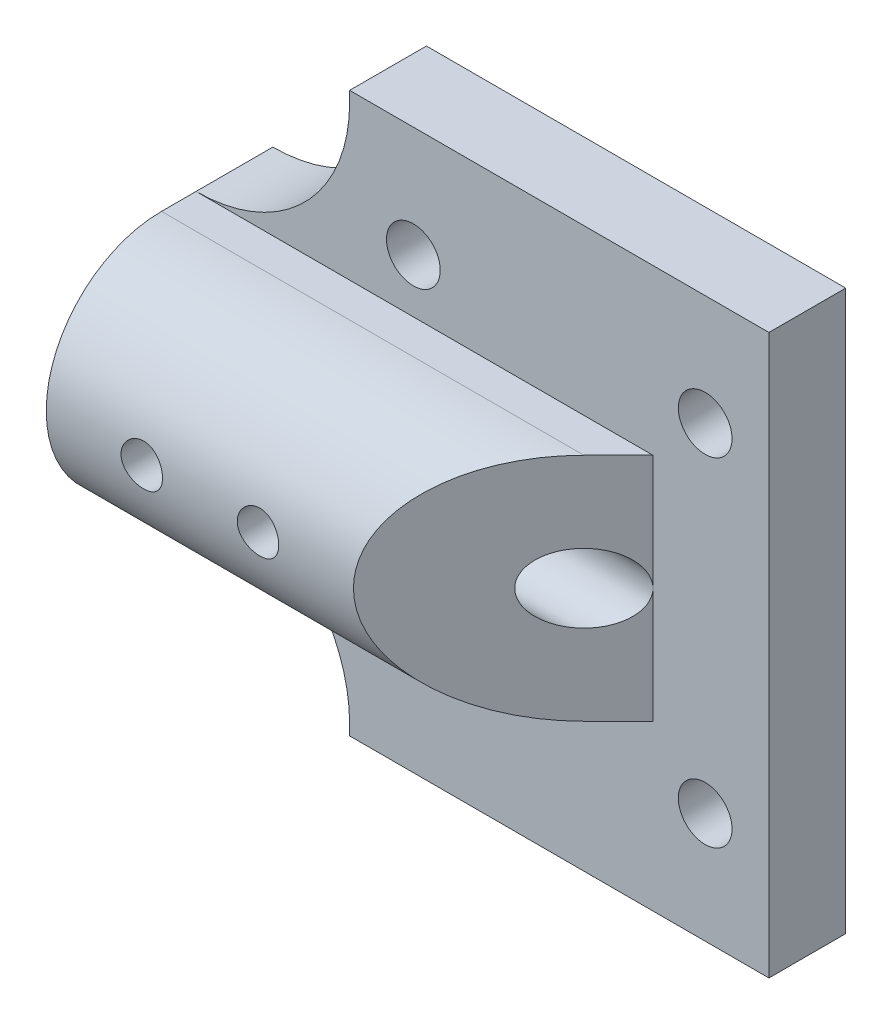
SolidWorks part; units mm, degrees
ref_plane "Front Plane" through (0, 0, 0) normal (0, 0, 1) x (1, 0, 0)
ref_plane "Top Plane" through (0, 0, 0) normal (0, 1, 0) x (1, 0, 0)
ref_plane "Right Plane" through (0, 0, 0) normal (1, 0, 0) x (0, 0, -1)
sketch "Sketch1" plane through (0, 0, 0) normal (0, 0, 1) x (1, 0, 0)
  line L0 (0, 18.2) -> (0, -18.2) construction
  line L1 (-13.65, -18.2) -> (13.65, -18.2)
  line L2 (-13.65, -18.2) -> (-13.65, 18.2) construction
  line L3 (-13.65, 18.2) -> (13.65, 18.2)
  line L4 (13.65, -18.2) -> (13.65, 18.2)
  line L5 (-13.65, -18.2) -> (13.65, 18.2) construction
  line L6 (-13.65, 18.2) -> (13.65, -18.2) construction
  line L7 (-13.65, 0) -> (13.65, 0) construction
  line L8 (-13.65, 0) -> (-23.65, 0) construction
  line L9 (-23.65, 2) -> (-23.65, -2) construction
  line L10 (-13.65, 2) -> (-23.65, 2) construction
  line L11 (-13.65, -2) -> (-23.65, -2) construction
  line L12 (-23.65, -7.5) -> (-23.65, 7.5)
  line L13 (-23.65, 7.5) -> (-13.65, 7.5)
  line L14 (-13.65, 7.5) -> (-13.65, 18.2)
  line L15 (-23.65, -7.5) -> (-13.65, -7.5)
  line L16 (-13.65, -7.5) -> (-13.65, -18.2)
  circle A0 centre (-9.5, 11) radius 1.75
  circle A1 centre (9.5, 11) radius 1.75
  circle A2 centre (-9.5, -11) radius 1.75
  circle A3 centre (9.5, -11) radius 1.75
  point P0 (0, 0)
  point P22 (-23.65, 0)
  point P27 (-23.65, 0)
  dimension "D3" = 3.5
  dimension "D4" = 11
  dimension "D5" = 9.5
  dimension "D1" = 36.4
  dimension "D2" = 27.3
  dimension "D6" = 4
  dimension "D7" = 10
  dimension "D8" = 15
extrude "Boss-Extrude1" add sketch "Sketch1" along normal blind 5
sketch "Sketch2" plane through (-23.65, 0, 0) normal (-1, 0, 0) x (0, 0, 1)
  line L0 (0, 0) -> (50000, 0) construction
  line L2 (5, 7.5) -> (5, -7.5) construction
  line L3 (5, 7.5) -> (5, -7.5)
  line L4 (5, 7.5) -> (7.25, 7.5)
  line L6 (7.25, -7.5) -> (5, -7.5)
  circle A0 centre (7.25, 0) radius 2.25 construction
  arc A1 (7.25, -7.5) -> (7.25, 7.5) centre (7.25, 0) ccw
  point P9 (9.5, 0)
  dimension "D1" = 4.5
  dimension "D3" = 15
extrude "Boss-Extrude4" add sketch "Sketch2" against normal blind 20
ref_plane "Plane1" through (0, 0, 14.75) normal (0, 0, 1) x (1, 0, 0)
sketch "Sketch7" plane through (0, 0, 14.75) normal (0, 0, 1) x (1, 0, 0)
  line L0 (-23.65, 0) -> (-18.7833, 0) construction
  line L1 (-23.65, 7.5) -> (-23.65, -7.5) construction
  line L2 (-16.0833, 0) -> (-11.2167, 0) construction
  line L3 (-8.5167, 0) -> (-3.65, 0) construction
  line L4 (-3.65, -7.5) -> (-3.65, 7.5) construction
  circle A0 centre (-17.4333, 0) radius 1.35
  circle A1 centre (-9.8667, 0) radius 1.35
  dimension "D1" = 2.7
extrude "Cut-Extrude3" cut sketch "Sketch7" against normal blind 7.5
chamfer "Chamfer2" distance 9.75 angle 45 1 edges at (-3.65, 0, 5)
sketch "Sketch6" plane through (-23.65, 0, 0) normal (-1, 0, 0) x (0, 0, 1)
  circle A0 centre (7.25, 0) radius 2.25
  dimension "D1" = 4.5
fillet "Fillet1" radius 10 2 edges at (-13.65, 7.5, 2.5) (-13.65, -7.5, 2.5)
extrude "Cut-Extrude2" cut sketch "Sketch6" against normal blind 43
chamfer "Chamfer3" distance 1 angle 45 1 edges at (-23.65, 0, 9.5)
